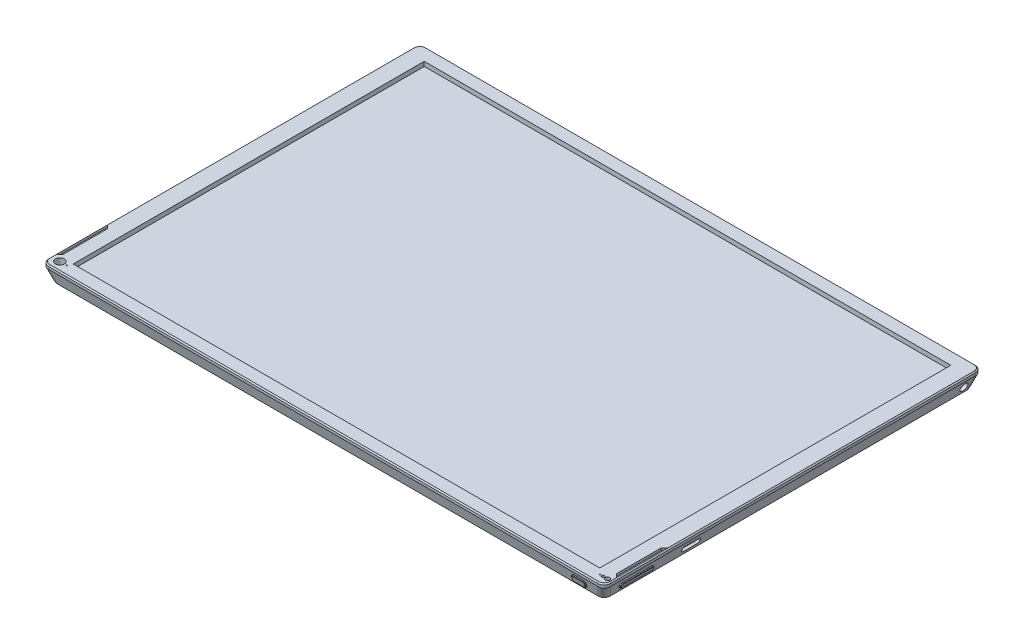
SolidWorks part; units mm, degrees
ref_plane "Front Plane" through (0, 0, 0) normal (0, 0, 1) x (1, 0, 0)
ref_plane "Top Plane" through (0, 0, 0) normal (0, 1, 0) x (1, 0, 0)
ref_plane "Right Plane" through (0, 0, 0) normal (1, 0, 0) x (0, 0, -1)
sketch "Sketch2" plane through (0, 0, 0) normal (0, 1, 0) x (1, 0, 0)
  line L1 (-129.4602, 62.5918) -> (123.2398, 62.5918)
  line L2 (-129.4602, 62.5918) -> (-129.4602, -107.2082)
  line L3 (-129.4602, -107.2082) -> (123.2398, -107.2082)
  line L4 (123.2398, 62.5918) -> (123.2398, -107.2082)
  dimension "D1" = 252.7
  dimension "D2" = 169.8
extrude "Boss-Extrude1" add sketch "Sketch2" along normal blind 7.3
sketch "Sketch3" plane through (-129.4602, 0, 0) normal (-1, 0, 0) x (0, 0, 1)
  line L0 (-62.5918, 5.7) -> (-60.5918, 0)
  line L1 (-62.5918, 7.3) -> (-62.5918, 0) construction
  line L2 (-62.5918, 0) -> (107.2082, 0) construction
  line L3 (-60.5918, 0) -> (-62.5918, 0)
  line L4 (-62.5918, 0) -> (-62.5918, 5.7)
  dimension "D1" = 1.6
  dimension "D2" = 2
extrude "Cut-Extrude1" cut sketch "Sketch3" against normal blind 267.3
sketch "Sketch4" plane through (-129.4602, 0, 0) normal (-1, 0, 0) x (0, 0, 1)
  line L0 (107.2082, 5.7) -> (105.2082, 0)
  line L1 (107.2082, 7.3) -> (107.2082, 0) construction
  line L2 (-60.5918, 0) -> (107.2082, 0) construction
  line L3 (105.2082, 0) -> (107.2082, 0)
  line L4 (107.2082, 0) -> (107.2082, 5.7)
  dimension "D1" = 1.6
  dimension "D2" = 2
extrude "Cut-Extrude2" cut sketch "Sketch4" against normal blind 267.3
ref_plane "Plane1" through (0, 0, 107.2082) normal (0, 0, 1) x (1, 0, 0)
sketch "Sketch5" plane through (0, 0, 107.2082) normal (0, 0, 1) x (1, 0, 0)
  line L0 (123.2398, 5.7) -> (121.2398, 0)
  line L1 (123.2398, 0) -> (-129.4602, 0) construction
  line L2 (121.2398, 0) -> (123.2398, 0)
  line L3 (123.2398, 0) -> (123.2398, 5.7)
  dimension "D1" = 2
extrude "Cut-Extrude3" cut sketch "Sketch5" against normal blind 267.3
sketch "Sketch6" plane through (0, 0, 107.2082) normal (0, 0, 1) x (1, 0, 0)
  line L0 (-129.4602, 5.7) -> (-127.4602, 0)
  line L1 (121.2398, 0) -> (-129.4602, 0) construction
  line L2 (-127.4602, 0) -> (-129.4602, 0)
  line L3 (-129.4602, 0) -> (-129.4602, 5.7)
  dimension "D1" = 2
extrude "Cut-Extrude4" cut sketch "Sketch6" against normal blind 267.3
fillet "Fillet1" radius 3 8 edges at (-128.4602, 2.85, -61.5918) (-129.4602, 6.5, -62.5918) (-128.4602, 2.85, 106.2082) (-129.4602, 6.5, 107.2082) (123.2398, 6.5, 107.2082) (122.2398, 2.85, 106.2082) (123.2398, 6.5, -62.5918) (122.2398, 2.85, -61.5918)
sketch "Sketch7" plane through (0, 7.3, 0) normal (0, 1, 0) x (1, 0, 0)
  line L0 (-129.4602, 59.5918) -> (-129.4602, -104.2082) construction
  line L1 (-121.4602, 56.5918) -> (115.2398, 56.5918)
  line L2 (-121.4602, 56.5918) -> (-121.4602, -101.2082)
  line L3 (-121.4602, -101.2082) -> (115.2398, -101.2082)
  line L4 (115.2398, 56.5918) -> (115.2398, -101.2082)
  line L5 (123.2398, -104.2082) -> (123.2398, 59.5918) construction
  line L6 (120.2398, 62.5918) -> (-126.4602, 62.5918) construction
  line L7 (-7.2086, -107.2082) -> (7.2086, -107.2082) construction
  dimension "D1" = 8
  dimension "D2" = 8
  dimension "D3" = 6
  dimension "D4" = 6
extrude "Cut-Extrude5" cut sketch "Sketch7" against normal blind 2
sketch "Sketch8" plane through (0, 0, 0) normal (0, -1, 0) x (1, 0, 0)
  line L0 (118.409, 105.2082) -> (-124.6294, 105.2082) construction
  line L1 (121.2398, -57.761) -> (121.2398, 102.3774) construction
  circle A0 centre (116.2398, 100.2082) radius 2.5
  dimension "D1" = 5
  dimension "D2" = 5
  dimension "D3" = 5
extrude "Cut-Extrude6" cut sketch "Sketch8" against normal blind 5
sketch "Sketch9" plane through (0, 0, 0) normal (0, -1, 0) x (1, 0, 0)
  circle A0 centre (116.2398, 100.2082) radius 3.5
  circle A1 centre (116.2398, 100.2082) radius 2.5 construction
  dimension "D1" = 1
extrude "Cut-Extrude7" cut sketch "Sketch9" against normal blind 1
sketch "Sketch10" plane through (0, 7.3, 0) normal (0, 1, 0) x (1, 0, 0)
  line L0 (-129.4602, 59.5918) -> (-129.4602, -104.2082) construction
  line L1 (-7.2086, -107.2082) -> (7.2086, -107.2082) construction
  circle A0 centre (-125.4602, -103.2082) radius 2
  dimension "D1" = 4
  dimension "D2" = 4
  dimension "D3" = 4
extrude "Cut-Extrude9" cut sketch "Sketch10" against normal blind 4
sketch "Sketch11" plane through (0, 7.3, 0) normal (0, 1, 0) x (1, 0, 0)
  line L0 (123.2398, -104.2082) -> (123.2398, 59.5918) construction
  circle A0 centre (121.2398, -103.6965) radius 1
  circle A1 centre (119.2398, -103.6965) radius 0.6
  dimension "D1" = 2
  dimension "D2" = 1.2
  dimension "D3" = 2
  dimension "D4" = 2
extrude "Cut-Extrude10" cut sketch "Sketch11" against normal blind 2
sketch "Sketch12" plane through (0, 7.3, 0) normal (0, 1, 0) x (1, 0, 0)
  circle A0 centre (117.8591, -103.6965) radius 0.25
  dimension "D1" = 0.5
extrude "Cut-Extrude11" cut sketch "Sketch12" against normal blind 2
sketch "Sketch13" plane through (0, 7.3, 0) normal (0, 1, 0) x (1, 0, 0)
  circle A0 centre (-122.4306, -103.2082) radius 0.25
  dimension "D1" = 0.5
extrude "Cut-Extrude12" cut sketch "Sketch13" against normal blind 2
chamfer "Chamfer1" distance 0.5 angle 45 8 edges at (-129.4602, 7.3, 22.3082) (-128.5815, 7.3, 106.3295) (-128.5815, 7.3, -61.7132) (-3.1102, 7.3, 107.2082) (-3.1102, 7.3, -62.5918) (122.3612, 7.3, 106.3295) (122.3612, 7.3, -61.7132) (123.2398, 7.3, 22.3082)
sketch "Sketch14" plane through (0, 7.3, 0) normal (0, 1, 0) x (1, 0, 0)
  line L0 (122.7398, -101.2082) -> (121.2398, -99.7082)
  line L1 (122.7398, -104.2082) -> (122.7398, 59.5918) construction
  line L2 (121.2398, -99.7082) -> (121.2398, -79.7082)
  line L3 (121.2398, -79.7082) -> (122.7398, -78.2082)
  line L4 (122.7398, -78.2082) -> (122.7398, -101.2082)
  dimension "D1" = 1.5
  dimension "D2" = 45
  dimension "D3" = 20
  dimension "D4" = 45
extrude "Cut-Extrude13" cut sketch "Sketch14" against normal blind 1
sketch "Sketch15" plane through (0, 7.3, 0) normal (0, 1, 0) x (1, 0, 0)
  line L0 (-128.9602, -101.2082) -> (-127.4602, -99.7082)
  line L1 (-128.9602, 59.5918) -> (-128.9602, -104.2082) construction
  line L2 (-127.4602, -99.7082) -> (-127.4602, -79.7082)
  line L3 (-127.4602, -79.7082) -> (-128.9602, -78.2082)
  line L4 (-128.9602, -78.2082) -> (-128.9602, -101.2082)
  dimension "D1" = 1.5
  dimension "D2" = 45
  dimension "D3" = 20
  dimension "D4" = 45
extrude "Cut-Extrude14" cut sketch "Sketch15" against normal blind 1
ref_plane "Plane2" through (-129.4602, 0, 0) normal (-1, 0, 0) x (0, 0, 1)
sketch "Sketch16" plane through (-129.4602, 0, 0) normal (-1, 0, 0) x (0, 0, 1)
  line L0 (-59.5918, 5.7) -> (104.2082, 5.7) construction
  line L1 (63.0082, 3.9) -> (71.2082, 3.9)
  line L2 (63.0082, 3.9) -> (63.0082, 1.4)
  line L3 (63.0082, 1.4) -> (71.2082, 1.4)
  line L4 (71.2082, 3.9) -> (71.2082, 1.4)
  line L6 (104.2082, 5.7) -> (104.2082, 6.8) construction
  dimension "D1" = 8.2
  dimension "D2" = 2.5
  dimension "D3" = 1.8
  dimension "D4" = 33
extrude "Cut-Extrude15" cut sketch "Sketch16" against normal blind 6
fillet "Fillet2" radius 1 4 edges at (-125.7058, 1.4, 71.2082) (-126.1444, 3.9, 71.2082) (-125.7058, 1.4, 63.0082) (-126.1444, 3.9, 63.0082)
sketch "Sketch17" plane through (-123.4602, 0, 0) normal (-1, 0, 0) x (0, 0, 1)
  line L0 (63.0082, 2.9) -> (63.0082, 2.4) construction
  line L1 (63.5082, 3.02) -> (70.7082, 3.02)
  line L2 (63.5082, 3.02) -> (63.5082, 2.32)
  line L3 (63.5082, 2.32) -> (70.7082, 2.32)
  line L4 (70.7082, 3.02) -> (70.7082, 2.32)
  line L5 (71.2082, 2.4) -> (71.2082, 2.9) construction
  line L6 (70.2082, 3.9) -> (64.0082, 3.9) construction
  dimension "D1" = 0.7
  dimension "D2" = 0.5
  dimension "D3" = 0.5
  dimension "D4" = 0.88
extrude "Boss-Extrude2" add sketch "Sketch17" along normal blind 4
fillet "Fillet3" radius 0.3 4 edges at (-125.4602, 2.32, 63.5082) (-125.4602, 3.02, 63.5082) (-125.4602, 2.32, 70.7082) (-125.4602, 3.02, 70.7082)
fillet "Fillet4" radius 0.1 8 edges at (-127.4602, 2.9321, 70.6203) (-127.4602, 2.67, 70.7082) (-127.4602, 2.4079, 70.6203) (-127.4602, 2.32, 67.1082) (-127.4602, 2.4079, 63.596) (-127.4602, 2.67, 63.5082) (-127.4602, 2.9321, 63.596) (-127.4602, 3.02, 67.1082)
ref_plane "Plane3" through (123.2398, 0, 0) normal (1, 0, 0) x (0, 0, -1)
sketch "Sketch18" plane through (123.2398, 0, 0) normal (1, 0, 0) x (0, 0, -1)
  line L0 (59.5918, 5.7) -> (-104.2082, 5.7) construction
  line L1 (-71.2082, 3.9) -> (-63.0082, 3.9)
  line L2 (-71.2082, 3.9) -> (-71.2082, 1.4)
  line L3 (-71.2082, 1.4) -> (-63.0082, 1.4)
  line L4 (-63.0082, 3.9) -> (-63.0082, 1.4)
  line L5 (-104.2082, 6.8) -> (-104.2082, 5.7) construction
  dimension "D1" = 8.2
  dimension "D2" = 2.5
  dimension "D3" = 1.8
  dimension "D4" = 33
extrude "Cut-Extrude16" cut sketch "Sketch18" against normal blind 6
fillet "Fillet5" radius 1 4 edges at (119.4855, 1.4, 63.0082) (119.9241, 3.9, 63.0082) (119.4855, 1.4, 71.2082) (119.9241, 3.9, 71.2082)
sketch "Sketch19" plane through (117.2398, 0, 0) normal (1, 0, 0) x (0, 0, -1)
  line L0 (-63.0082, 2.4) -> (-63.0082, 2.9) construction
  line L1 (-70.7082, 3) -> (-63.5082, 3)
  line L2 (-70.7082, 3) -> (-70.7082, 2.3)
  line L3 (-70.7082, 2.3) -> (-63.5082, 2.3)
  line L4 (-63.5082, 3) -> (-63.5082, 2.3)
  line L5 (-71.2082, 2.9) -> (-71.2082, 2.4) construction
  line L6 (-70.2082, 1.4) -> (-64.0082, 1.4) construction
  dimension "D1" = 0.7
  dimension "D2" = 0.5
  dimension "D3" = 0.5
  dimension "D4" = 0.9
extrude "Boss-Extrude3" add sketch "Sketch19" along normal blind 4
fillet "Fillet6" radius 0.3 4 edges at (119.2398, 2.3, 63.5082) (119.2398, 3, 63.5082) (119.2398, 2.3, 70.7082) (119.2398, 3, 70.7082)
fillet "Fillet7" radius 0.1 8 edges at (121.2398, 2.9121, 63.596) (121.2398, 2.65, 63.5082) (121.2398, 2.3879, 63.596) (121.2398, 2.3, 67.1082) (121.2398, 2.3879, 70.6203) (121.2398, 2.65, 70.7082) (121.2398, 2.9121, 70.6203) (121.2398, 3, 67.1082)
sketch "Sketch20" plane through (107.9496, -37.8771, 0) normal (0.9436, -0.3311, 0) x (0, 0, -1)
  line L0 (59.5918, 46.1817) -> (-104.2082, 46.1817) construction
  line L1 (-99.4357, 44.1817) -> (-84.4357, 44.1817)
  line L2 (-99.4357, 44.1817) -> (-99.4357, 42.1817)
  line L3 (-99.4357, 42.1817) -> (-84.4357, 42.1817)
  line L4 (-84.4357, 44.1817) -> (-84.4357, 42.1817)
  dimension "D1" = 2
  dimension "D2" = 15
  dimension "D3" = 2
extrude "Boss-Extrude4" add sketch "Sketch20" along normal blind 0.6
fillet "Fillet8" radius 0.6 4 edges at (122.1986, 1.8263, 84.4357) (122.8608, 3.7135, 84.4357) (122.1986, 1.8263, 99.4357) (122.8608, 3.7135, 99.4357)
chamfer "Chamfer2" distance 0.2 angle 45 8 edges at (122.4817, 1.7269, 91.9357) (122.5398, 1.8928, 84.6114) (122.5398, 1.8928, 99.2599) (122.8127, 2.6705, 84.4357) (122.8127, 2.6705, 99.4357) (123.0856, 3.4483, 84.6114) (123.0856, 3.4483, 99.2599) (123.1438, 3.6141, 91.9357)
sketch "Sketch21" plane through (0, -32.8685, 93.6753) normal (0, -0.3311, 0.9436) x (1, 0, 0)
  line L0 (120.2398, 40.8738) -> (-126.4602, 40.8738) construction
  line L1 (108.2398, 39.3738) -> (114.2398, 39.3738)
  line L2 (108.2398, 39.3738) -> (108.2398, 36.3738)
  line L3 (108.2398, 36.3738) -> (114.2398, 36.3738)
  line L4 (114.2398, 39.3738) -> (114.2398, 36.3738)
  line L5 (120.2398, 40.8738) -> (120.2398, 41.9118) construction
  dimension "D1" = 3
  dimension "D2" = 6
  dimension "D3" = 1.5
  dimension "D4" = 6
extrude "Boss-Extrude5" add sketch "Sketch21" along normal blind 0.6
fillet "Fillet9" radius 0.6 4 edges at (108.2398, 1.3545, 106.0013) (108.2398, 4.1853, 106.9946) (114.2398, 1.3545, 106.0013) (114.2398, 4.1853, 106.9946)
chamfer "Chamfer3" distance 0.2 angle 45 8 edges at (111.2398, 1.2551, 106.2844) (114.0641, 1.421, 106.3426) (108.4156, 1.421, 106.3426) (114.2398, 2.6705, 106.7811) (108.2398, 2.6705, 106.7811) (114.0641, 3.9201, 107.2195) (108.4156, 3.9201, 107.2195) (111.2398, 4.0859, 107.2777)
sketch "Sketch22" plane through (123.2398, 0, 0) normal (1, 0, 0) x (0, 0, -1)
  line L0 (59.5918, 5.7) -> (59.5918, 6.8) construction
  circle A0 centre (55.5918, 2.7004) radius 1.75
  dimension "D1" = 3.5
  dimension "D2" = 4
extrude "Cut-Extrude17" cut sketch "Sketch22" against normal blind 8
fillet "Fillet10" radius 1 1 edges at (115.2398, 2.7004, -57.3418)
